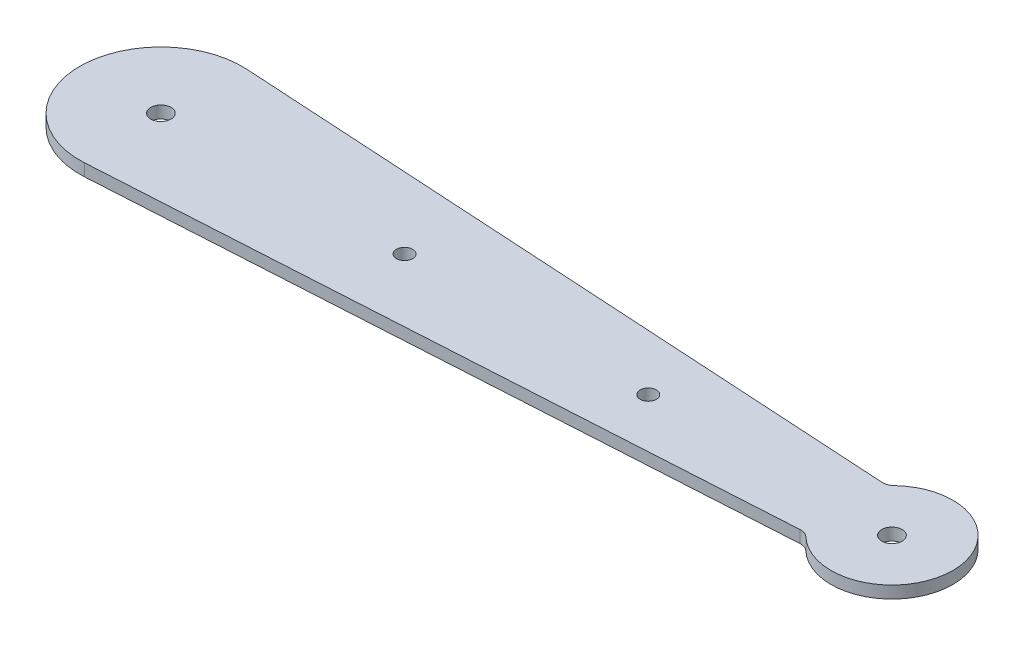
SolidWorks part; units mm, degrees
ref_plane "Front Plane" through (0, 0, 0) normal (0, 0, 1) x (1, 0, 0)
ref_plane "Top Plane" through (0, 0, 0) normal (0, 1, 0) x (1, 0, 0)
ref_plane "Right Plane" through (0, 0, 0) normal (1, 0, 0) x (0, 0, -1)
sketch "Sketch1" plane through (0, 0, 0) normal (0, 1, 0) x (1, 0, 0)
  line L0 (0, 0) -> (180, 0) construction
  line L1 (168.8197, 10) -> (1.1868, 19.9648)
  line L2 (168.8197, -10) -> (1.1868, -19.9648)
  circle A0 centre (0, 0) radius 20
  circle A1 centre (180, 0) radius 15
  circle A2 centre (0, 0) radius 2.5
  circle A3 centre (180, 0) radius 2.5
  circle A4 centre (60, 0) radius 2
  circle A5 centre (120, 0) radius 2
  dimension "D1" = 40
  dimension "D2" = 30
  dimension "D6" = 60
  dimension "D8" = 5
  dimension "D9" = 4
  dimension "D10" = 4
  dimension "D11" = 5
  dimension "D3" = 180
  dimension "D4" = 10
  dimension "D5" = 10
  dimension "D7" = 120
extrude "Boss-Extrude1" add sketch "Sketch1" along normal blind 3 contours A2 A0 | A0 L0 A4 A5 A1 L1 | L0 A0 L2 A1 A5 A4 | A1 A3 region at (14.144, 0, 13.3282) region at (83.3917, 0, -7.7749) region at (83.3917, 0, 7.7749) region at (185.2009, 0, -13.6162)
fillet "Fillet2" radius 3 1 edges at (168.8197, 1.5, -10) type face fillet first side face at (85.0032, 1.5, -14.9824) second side face at (181.9098, 1.5, 0)
fillet "Fillet3" radius 3 1 edges at (168.8197, 1.5, 10) type face fillet first side face at (85.0032, 1.5, 14.9824) second side face at (182.1213, 1.5, 0.0885)
